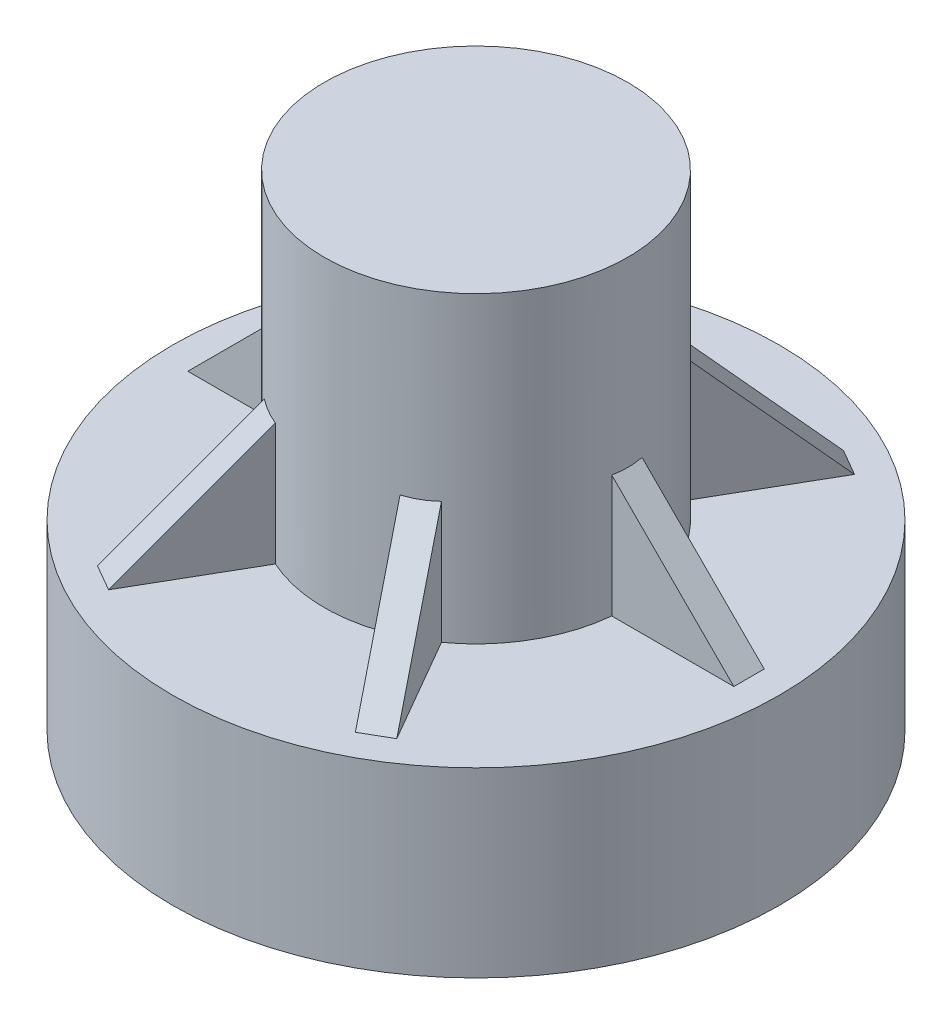
SolidWorks part; units mm, degrees
ref_plane "Plane1" through (0, 0, 0) normal (0, 0, 1) x (1, 0, 0)
ref_plane "Plane2" through (0, 0, 0) normal (0, 1, 0) x (1, 0, 0)
ref_plane "Plane3" through (0, 0, 0) normal (1, 0, 0) x (0, 0, -1)
sketch "Эскиз1" plane through (0, 0, 0) normal (0, 1, 0) x (1, 0, 0)
  circle A0 centre (0, 0) radius 50
  dimension "D1" = 100
extrude "Основание-Вытянуть" add sketch "Эскиз1" along normal blind 30
sketch "Эскиз2" plane through (0, 30, 0) normal (0, 1, 0) x (-1, 0, 0)
  circle A0 centre (0, 0) radius 25
  dimension "D1" = 50
extrude "Бобышка-Вытянуть1" add sketch "Эскиз2" along normal blind 50
sketch "Sketch4" plane through (0, 0, 0) normal (0, 0, 1) x (1, 0, 0)
  line L0 (25, 50) -> (45, 30)
  line L2 (50, 30) -> (-50, 30) construction
  line L3 (25, 30) -> (25, 80) construction
  dimension "D1" = 45
  dimension "D2" = 20
rib "Rib8" sketch "Sketch4" sketch "Sketch4" thickness 5 extrusion direction parallel to sketch draft on no parameters "D1"=5
ref_plane "Plane4" [suppressed] through (0, 0, 0) normal (1, 0, 0) x (0, 0, -1)
mirror "Mirror1" [suppressed] about plane through (0, 0, 0) normal (1, 0, 0)
scale "Scale1" scale about centroid uniform scaling yes scale factor 2
pattern_circular "CirPattern6" count 6 over 360 about axis through (-0.0949, 133.2056, 0) along (0, 1, 0) of face at (63.0714, 46.6224, 5) of face at (63.0714, 46.6224, -5) of face at (69.8424, 53.2682, 0)
